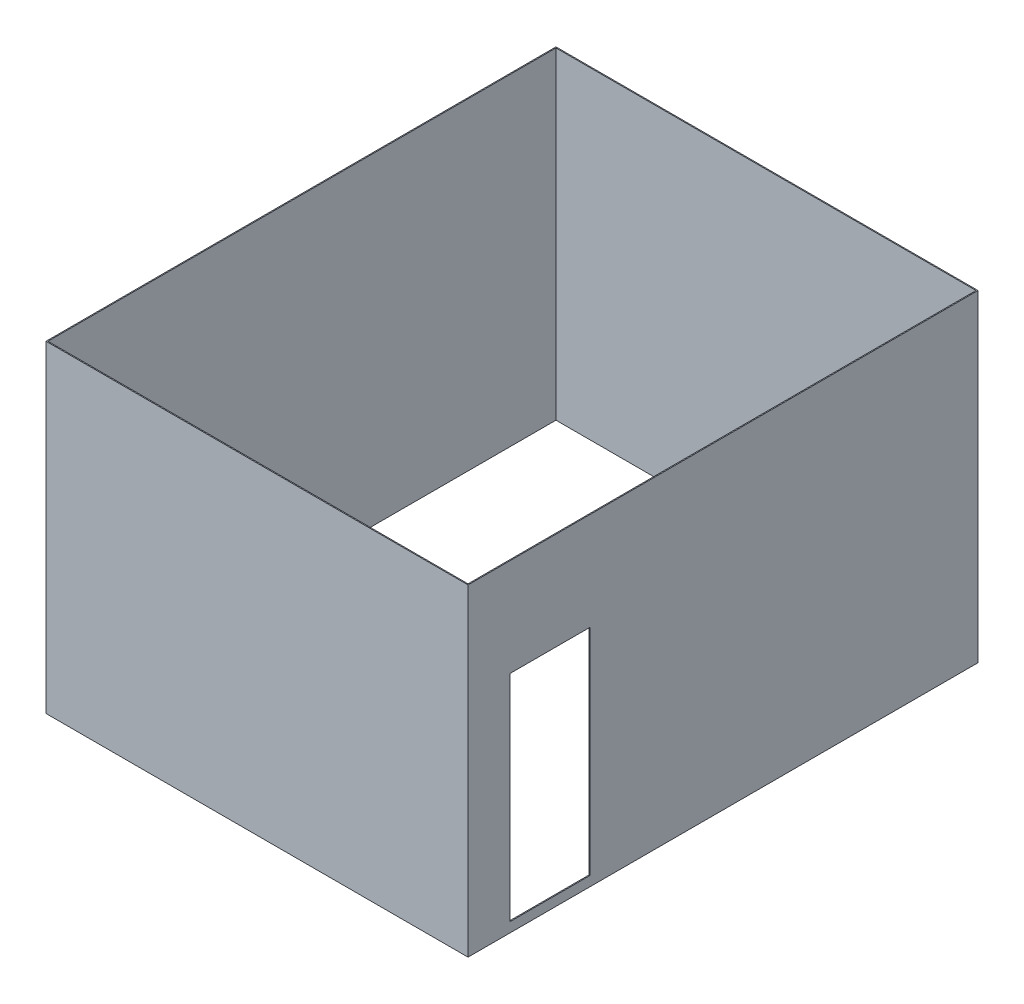
SolidWorks part; units mm, degrees
ref_plane "Спереди" through (0, 0, 0) normal (0, 0, 1) x (1, 0, 0)
ref_plane "Сверху" through (0, 0, 0) normal (0, 1, 0) x (1, 0, 0)
ref_plane "Справа" through (0, 0, 0) normal (1, 0, 0) x (0, 0, -1)
sketch "Эскиз1" plane through (0, 0, 0) normal (0, 1, 0) x (1, 0, 0)
  line L1 (0, 0) -> (-430, 0)
  line L2 (0, 0) -> (0, 520)
  line L3 (0, 520) -> (-430, 520)
  line L4 (-430, 0) -> (-430, 520)
  dimension "D1" = 520
  dimension "D2" = 430
extrude "Вытянуть-Тонкостенный2" add sketch "Эскиз1" along normal blind 330 thin thin type one direction wall 1
sketch "Эскиз2" plane through (1, 0, 0) normal (1, 0, 0) x (0, 0, -1)
  line L0 (-1, 0) -> (521, 0) construction
  line L1 (42, 10) -> (124, 10)
  line L2 (42, 10) -> (42, 230)
  line L3 (42, 230) -> (124, 230)
  line L4 (124, 10) -> (124, 230)
  line L5 (-1, 330) -> (-1, 0) construction
  dimension "D1" = 10
  dimension "D2" = 220
  dimension "D3" = 82
  dimension "D4" = 43
extrude "Вырез-Вытянуть2" cut sketch "Эскиз2" against normal blind 10
